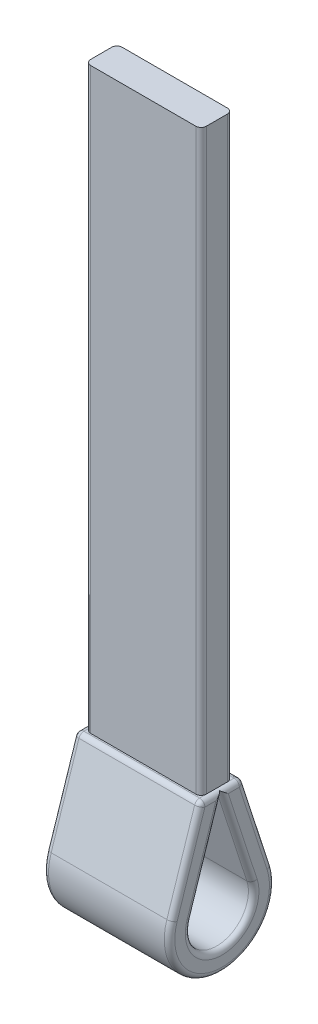
SolidWorks part; units mm, degrees
ref_plane "Front Plane" through (0, 0, 0) normal (0, 0, 1) x (1, 0, 0)
ref_plane "Top Plane" through (0, 0, 0) normal (0, 1, 0) x (1, 0, 0)
ref_plane "Right Plane" through (0, 0, 0) normal (1, 0, 0) x (0, 0, -1)
sketch "Sketch1" plane through (0, 0, 0) normal (1, 0, 0) x (0, 0, -1)
  line L0 (-5.7047, 1.8591) -> (0, 19.3647)
  line L1 (-9.5079, 3.0984) -> (-4, 20)
  line L2 (-4, 20) -> (-4, 60)
  line L3 (-4, 60) -> (4, 60)
  line L4 (4, 20) -> (4, 60)
  line L5 (-4, 20) -> (4, 20) construction
  line L6 (4, 20) -> (9.5079, 3.0984)
  line L7 (0, 19.3647) -> (5.7047, 1.8591)
  circle A0 centre (0, 0) radius 6 construction
  arc A1 (-9.5079, 3.0984) -> (9.5079, 3.0984) centre (0, 0) ccw
  arc A2 (-5.7047, 1.8591) -> (5.7047, 1.8591) centre (0, 0) ccw
  circle A3 centre (0, 0) radius 10 construction
  point P10 (10, 0)
  dimension "D1" = 12
  dimension "D3" = 8
  dimension "D4" = 30
  dimension "D5" = 40
  dimension "D2" = 4
extrude "Boss-Extrude1" add sketch "Sketch1" along normal blind 24
sketch "Sketch2" plane through (0, 60, 0) normal (0, 1, 0) x (1, 0, 0)
  line L4 (0, 4) -> (0, -4)
  line L5 (0, -4) -> (24, -4)
  line L6 (24, -4) -> (24, 4)
  line L7 (24, 4) -> (0, 4)
  line L8 (0, 4) -> (0, -4)
  line L9 (0, -4) -> (24, -4)
  line L10 (24, -4) -> (24, 4)
  line L11 (24, 4) -> (0, 4)
  line L16 (1, 3) -> (1, -3)
  line L17 (1, -3) -> (23, -3)
  line L18 (23, -3) -> (23, 3)
  line L19 (23, 3) -> (1, 3)
  line L20 (1, 3) -> (1, -3)
  line L21 (1, -3) -> (23, -3)
  line L22 (23, -3) -> (23, 3)
  line L23 (23, 3) -> (1, 3)
  dimension "D1" = 0
  dimension "D2" = 1
extrude "Cut-Extrude1" cut sketch "Sketch2" against normal up to vertex (40 mm away) up to point (0, 20, 4)
fillet "Fillet1" radius 1 16 edges at (24, 10.6119, -2.8524) (24, -6, 0) (24, 11.5492, -6.7539) (24, -10, 0) (0, 10.6119, 2.8524) (0, -6, 0) (0, 11.5492, -6.7539) (0, -10, 0) (24, 10.6119, 2.8524) (24, 20, 0) (24, 11.5492, 6.7539) (12, 20, -4) (12, 20, 4) (0, 10.6119, -2.8524) (0, 20, 0) (0, 11.5492, 6.7539)
fillet "Fillet2" radius 1 4 edges at (1, 40, -3) (1, 40, 3) (23, 40, -3) (23, 40, 3)
sketch "Sketch3" plane through (0, 60, 0) normal (0, 1, 0) x (1, 0, 0)
  line L4 (22, 3) -> (2, 3)
  line L5 (1, 2) -> (1, -2)
  line L6 (2, -3) -> (22, -3)
  line L7 (23, -2) -> (23, 2)
  line L8 (22, 3) -> (2, 3)
  line L9 (1, 2) -> (1, -2)
  line L10 (2, -3) -> (22, -3)
  line L11 (23, -2) -> (23, 2)
  arc A4 (2, 3) -> (1, 2) centre (2, 2) ccw
  arc A5 (1, -2) -> (2, -3) centre (2, -2) ccw
  arc A6 (22, -3) -> (23, -2) centre (22, -2) ccw
  arc A7 (23, 2) -> (22, 3) centre (22, 2) ccw
  arc A8 (2, 3) -> (1, 2) centre (2, 2) ccw
  arc A9 (1, -2) -> (2, -3) centre (2, -2) ccw
  arc A10 (22, -3) -> (23, -2) centre (22, -2) ccw
  arc A11 (23, 2) -> (22, 3) centre (22, 2) ccw
  dimension "D1" = 0
extrude "Boss-Extrude2" add sketch "Sketch3" along normal blind 70
